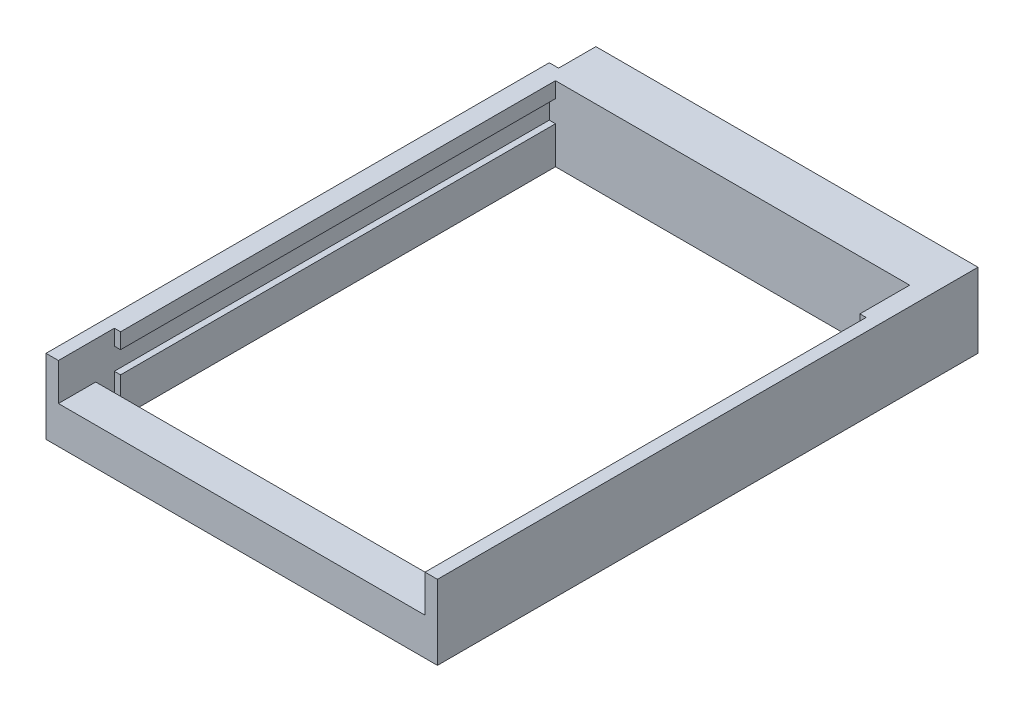
SolidWorks part; units mm, degrees
ref_plane "前视基准面" through (0, 0, 0) normal (0, 0, 1) x (1, 0, 0)
ref_plane "上视基准面" through (0, 0, 0) normal (0, 1, 0) x (1, 0, 0)
ref_plane "右视基准面" through (0, 0, 0) normal (1, 0, 0) x (0, 0, -1)
other "Configuration Table"
sketch "草图1" plane through (0, 0, 0) normal (0, 1, 0) x (1, 0, 0)
  line L1 (-14.75, 19.75) -> (14.75, 19.75)
  line L2 (-14.75, 19.75) -> (-14.75, -19.75)
  line L3 (-14.75, -19.75) -> (14.75, -19.75)
  line L4 (14.75, 19.75) -> (14.75, -19.75)
  line L5 (-14.75, 19.75) -> (14.75, -19.75) construction
  line L6 (-14.75, -19.75) -> (14.75, 19.75) construction
  line L7 (-15.75, -19.75) -> (15.75, -19.75)
  line L8 (-15.75, -19.75) -> (-15.75, 23.75)
  line L9 (-15.75, 23.75) -> (15.75, 23.75)
  line L10 (15.75, -19.75) -> (15.75, 23.75)
  point P0 (0, 0)
  dimension "D1" = 29.5
  dimension "D2" = 39.5
  dimension "D3" = 1
  dimension "D4" = 1
  dimension "D5" = 4
extrude "凸台-拉伸1" add sketch "草图1" along normal blind 3 and the other way blind 3 contours L7 L10 L9 L8 L2 L1 L4 region at (-15.2871, 0, 0)
sketch "草图2" plane through (0, 0, -19.75) normal (0, 0, 1) x (1, 0, 0)
  line L0 (-14.75, -3) -> (14.75, -3) construction
  line L1 (-14.75, 3) -> (-14.25, 3)
  line L2 (-14.75, 3) -> (-14.75, -3)
  line L3 (-14.75, -3) -> (-14.25, -3)
  line L4 (-14.25, 3) -> (-14.25, -3)
  line L5 (-14.75, 0) -> (-14.75, 1.75)
  line L6 (0, 3) -> (0, -3) construction
  line L7 (-14.75, 1.75) -> (-14.25, 1.75)
  line L8 (-14.75, 1.75) -> (-14.75, 0)
  line L9 (-14.75, 0) -> (-14.25, 0)
  line L10 (-14.25, 1.75) -> (-14.25, 0)
  line L11 (14.75, 0) -> (14.25, 0)
  line L12 (14.25, 1.75) -> (14.25, 0)
  line L13 (14.75, 1.75) -> (14.25, 1.75)
  line L14 (14.75, 1.75) -> (14.75, 0)
  line L15 (14.75, -3) -> (14.25, -3)
  line L16 (14.25, 3) -> (14.25, -3)
  line L17 (14.75, 3) -> (14.25, 3)
  line L18 (14.75, 3) -> (14.75, -3)
  point P16 (0, 0)
  point P25 (0, 0)
  line M4 (14.75, -3) -> (14.75, 3)
  line M5 (14.75, 3) -> (-14.75, 3)
  line M6 (-14.75, 3) -> (-14.75, -3)
  line M7 (-14.75, -3) -> (14.75, -3)
  dimension "D1" = 0.5
  dimension "D2" = 1.75
  dimension "D3" = 3
extrude "凸台-拉伸2" add sketch "草图2" along normal blind 35 contours L9 L4 M6 M7 | L7 L4 M6 M5 | L11 L16 M7 M4 region at (-14.5, 2.375, -19.75) region at (-14.5, -1.5, -19.75) region at (14.5, -1.5, -19.75)
sketch "草图3" plane through (0, 0, -23.75) normal (0, 0, -1) x (-1, 0, 0)
  line L0 (15.75, -3) -> (-15.75, -3) construction
  line L1 (-12.25, -3) -> (-6.25, -3)
  line L2 (-12.25, -3) -> (-12.25, 0)
  line L3 (-12.25, 0) -> (-6.25, 0)
  line L4 (-6.25, -3) -> (-6.25, 0)
  line L5 (-15.75, -3) -> (-15.75, 3) construction
  line L10 (0, 3) -> (0, -3) construction
  line L11 (15.75, 3) -> (-15.75, 3) construction
  line L12 (12.25, 0) -> (6.25, 0)
  line L13 (6.25, -3) -> (6.25, 0)
  line L14 (12.25, -3) -> (6.25, -3)
  line L15 (12.25, -3) -> (12.25, 0)
  dimension "D1" = 3.5
  dimension "D2" = 6
  dimension "D3" = 3
extrude "切除-拉伸1" cut sketch "草图3" against normal blind 1.5
sketch "草图4" plane through (0, 3, 0) normal (0, 1, 0) x (1, 0, 0)
  line L1 (-15.75, 23.75) -> (-15, 23.75)
  line L2 (-15.75, 23.75) -> (-15.75, 20.75)
  line L3 (-15.75, 20.75) -> (-15, 20.75)
  line L4 (-15, 23.75) -> (-15, 20.75)
  dimension "D1" = 3
  dimension "D2" = 0.75
extrude "切除-拉伸2" cut sketch "草图4" against normal up to next
extrude "凸台-拉伸3" add sketch "草图2<4>" along normal blind 4 contours L16 L13 M5 M4 region at (14.5, 2.375, -19.75)
sketch "草图2<4>" plane through (0, 0, -19.75) normal (0, 0, 1) x (1, 0, 0) same geometry as "草图2"
sketch "草图5" plane through (-14.75, 0, 0) normal (1, 0, 0) x (0, 0, -1)
  line L1 (-19.75, -3) -> (-16.75, -3)
  line L2 (-19.75, -3) -> (-19.75, 0)
  line L3 (-19.75, 0) -> (-16.75, 0)
  line L4 (-16.75, -3) -> (-16.75, 0)
  dimension "D1" = 3
  dimension "D2" = 3
extrude "凸台-拉伸4" add sketch "草图5" along normal up to next
